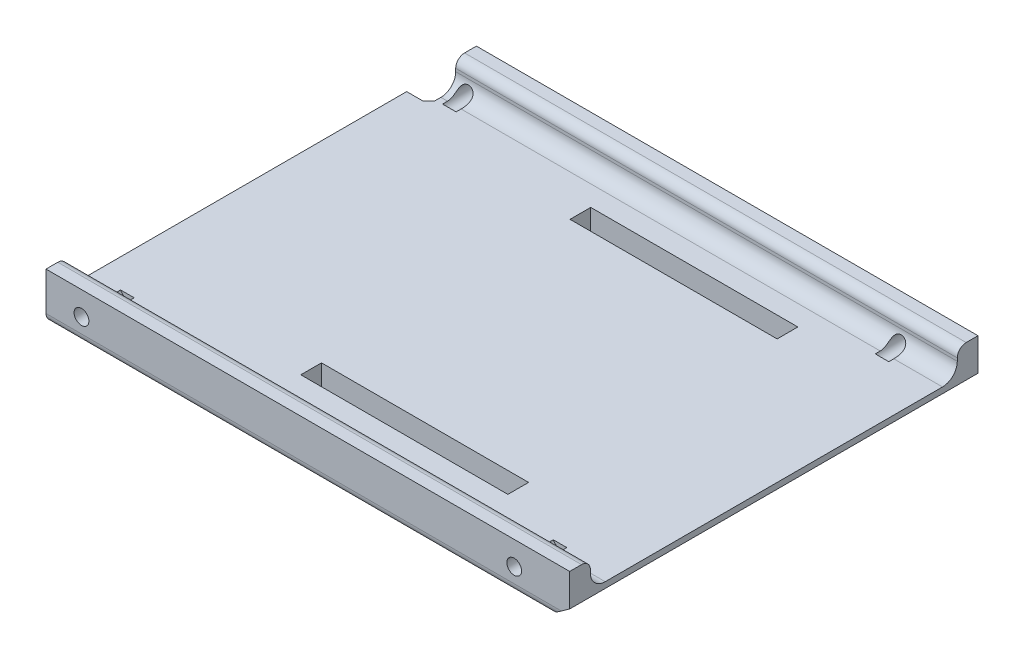
SolidWorks part; units mm, degrees
ref_plane "Front Plane" through (0, 0, 0) normal (0, 0, 1) x (1, 0, 0)
ref_plane "Top Plane" through (0, 0, 0) normal (0, 1, 0) x (1, 0, 0)
ref_plane "Right Plane" through (0, 0, 0) normal (1, 0, 0) x (0, 0, -1)
other "Graphic1"
other "Graphic (Closed) -1"
sketch "Sketch2" plane through (0, 0, 0) normal (0, 0, 1) x (1, 0, 0)
  line L0 (0, 0) -> (0, 8)
  line L1 (0, 8) -> (88.5, 8)
  line L2 (88.5, 8) -> (88.5, 2.5)
  line L3 (88.5, 2.5) -> (85, 0)
  line L4 (85, 0) -> (0, 0)
  circle A0 centre (6, 4) radius 1.25
  circle A1 centre (79.1209, 4) radius 1.25
  dimension "D1" = 2.5
  dimension "D2" = 2.5
  dimension "D3" = 73.1209
  dimension "D4" = 4
  dimension "D5" = 8
  dimension "D6" = 5.5
  dimension "D7" = 85
  dimension "D8" = 2.5
  dimension "D9" = 3.5
extrude "Boss-Extrude1" add sketch "Sketch2" along normal blind 69
sketch "Sketch3" plane through (0, 0, 0) normal (-1, 0, 0) x (0, 0, 1)
  line L0 (69, 8) -> (0, 8) construction
  line L1 (3.5, 8) -> (65.5, 8)
  line L2 (3.5, 8) -> (3.5, 3.5)
  line L3 (3.5, 3.5) -> (65.5, 3.5)
  line L4 (65.5, 8) -> (65.5, 3.5)
  line L5 (0, 8) -> (0, 0) construction
  line L6 (69, 8) -> (69, 0) construction
  line L7 (69, 0) -> (0, 0) construction
  dimension "D1" = 3.5
  dimension "D2" = 3.5
  dimension "D3" = 3.5
extrude "Cut-Extrude1" cut sketch "Sketch3" against normal through all
sketch "Sketch4" plane through (0, 0, 0) normal (-1, 0, 0) x (0, 0, 1)
  line L0 (3.5, 3.5) -> (65.5, 3.5) construction
  line L1 (6.8442, 3.5) -> (61.2506, 3.5)
  line L2 (6.8442, 3.5) -> (6.8442, 1.0826)
  line L3 (6.8442, 1.0826) -> (61.2506, 1.0826)
  line L4 (61.2506, 3.5) -> (61.2506, 1.0826)
extrude "Boss-Extrude2" add sketch "Sketch4" against normal blind 83
fillet "Fillet1" radius 1.5 2 edges at (42.5, 0, 0) (42.5, 0, 69)
fillet "Fillet2" radius 2.5 2 edges at (84.3833, 3.5, 3.5) (84.3833, 3.5, 65.5)
fillet "Fillet3" radius 1.5 2 edges at (44.25, 8, 3.5) (44.25, 8, 65.5)
sketch "Sketch6" plane through (0, 0, 0) normal (0, -1, 0) x (1, 0, 0)
  line L0 (-1.3983, 8.0506) -> (2.8006, 8.0506)
  line L1 (2.8006, 8.0506) -> (3.7366, 7.0279)
  line L2 (3.7366, 7.0279) -> (3.7366, 1.0984)
  line L3 (3.7366, 1.0984) -> (3.7366, 0)
  line L4 (3.7366, 0) -> (-1.2361, -1.1395)
  line L5 (-1.2361, -1.1395) -> (-1.3983, 8.0506)
  line L6 (87.1, 0) -> (0, 0) construction
extrude "Cut-Extrude3" cut sketch "Sketch6" against normal through all
sketch "Sketch7" plane through (0, 0, 0) normal (0, -1, 0) x (1, 0, 0)
  line L1 (32.5, 58.4459) -> (67.5, 58.4459)
  line L2 (32.5, 58.4459) -> (32.5, 54.9459)
  line L3 (32.5, 54.9459) -> (67.5, 54.9459)
  line L4 (67.5, 58.4459) -> (67.5, 54.9459)
  line L5 (32.5, 12.9459) -> (67.5, 12.9459)
  line L6 (32.5, 12.9459) -> (32.5, 9.4459)
  line L7 (32.5, 9.4459) -> (67.5, 9.4459)
  line L8 (67.5, 12.9459) -> (67.5, 9.4459)
extrude "Cut-Extrude5" cut sketch "Sketch7" against normal up to next
